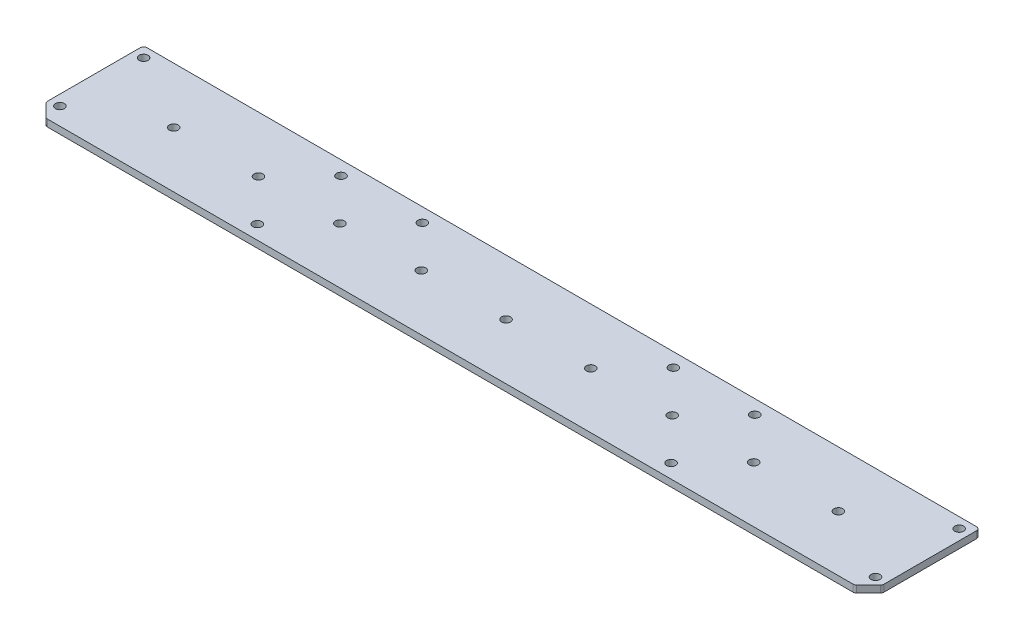
SolidWorks part; units mm, degrees
ref_plane "Front Plane" through (0, 0, 0) normal (0, 0, 1) x (1, 0, 0)
ref_plane "Top Plane" through (0, 0, 0) normal (0, 1, 0) x (1, 0, 0)
ref_plane "Right Plane" through (0, 0, 0) normal (1, 0, 0) x (0, 0, -1)
sketch "Sketch2" plane through (0, 0, 0) normal (0, 1, 0) x (1, 0, 0)
  line L0 (0, 7.0076) -> (0, 50.8)
  line L1 (0, 50.8) -> (381, 50.8)
  line L2 (381, 50.8) -> (381, 7.0076)
  line L3 (373.9924, 0) -> (7.0076, 0)
  line L4 (5.885, 0.465) -> (0.465, 5.885) construction
  line L5 (5.885, 0.465) -> (0.465, 5.885)
  line L6 (375.115, 0.465) -> (380.535, 5.885) construction
  line L7 (375.115, 0.465) -> (380.535, 5.885)
  line L8 (336.537, 50.8) -> (379.4125, 50.8) construction
  arc A0 (5.885, 0.465) -> (7.0076, 0) centre (7.0076, 1.5875) ccw construction
  arc A1 (0, 7.0076) -> (0.465, 5.885) centre (1.5875, 7.0076) ccw construction
  arc A2 (5.885, 0.465) -> (7.0076, 0) centre (7.0076, 1.5875) ccw
  arc A3 (0, 7.0076) -> (0.465, 5.885) centre (1.5875, 7.0076) ccw
  arc A4 (373.9924, 0) -> (375.115, 0.465) centre (373.9924, 1.5875) ccw construction
  arc A6 (373.9924, 0) -> (375.115, 0.465) centre (373.9924, 1.5875) ccw
  arc A8 (380.535, 5.885) -> (381, 7.0076) centre (379.4125, 7.0076) ccw construction
  arc A9 (380.535, 5.885) -> (381, 7.0076) centre (379.4125, 7.0076) ccw
extrude "Boss-Extrude1" add sketch "Sketch2" along normal blind 3.175
sketch "Sketch3" plane through (0, 0, 0) normal (0, 1, 0) x (1, 0, 0)
  circle A25 centre (4.7625, 7.9375) radius 2.032 construction
  circle A31 centre (4.7625, 46.0375) radius 2.032 construction
  circle A63 centre (376.2375, 7.9375) radius 2.032 construction
  circle A64 centre (376.2375, 46.0375) radius 2.032 construction
  circle A67 centre (4.7625, 7.9375) radius 2.032
  circle A68 centre (4.7625, 46.0375) radius 2.032
  circle A72 centre (376.2375, 7.9375) radius 2.032
  circle A73 centre (376.2375, 46.0375) radius 2.032
  circle A123 centre (341.884, 25.4) radius 2.032 construction
  circle A124 centre (247.65, 44.45) radius 2.032 construction
  circle A125 centre (284.734, 44.45) radius 2.032 construction
  circle A129 centre (284.734, 6.35) radius 2.032 construction
  circle A132 centre (190.5, 25.4) radius 2.032 construction
  circle A135 centre (133.35, 44.45) radius 2.032 construction
  circle A136 centre (96.266, 44.45) radius 2.032 construction
  circle A137 centre (96.266, 6.35) radius 2.032 construction
  circle A140 centre (77.724, 25.4) radius 2.032 construction
  circle A141 centre (39.116, 25.4) radius 2.032 construction
  circle A142 centre (341.884, 25.4) radius 2.032
  circle A143 centre (247.65, 44.45) radius 2.032
  circle A144 centre (284.734, 44.45) radius 2.032
  circle A148 centre (284.734, 6.35) radius 2.032
  circle A151 centre (190.5, 25.4) radius 2.032
  circle A154 centre (133.35, 44.45) radius 2.032
  circle A155 centre (96.266, 44.45) radius 2.032
  circle A156 centre (96.266, 6.35) radius 2.032
  circle A159 centre (77.724, 25.4) radius 2.032
  circle A160 centre (39.116, 25.4) radius 2.032
  circle A161 centre (151.892, 25.4) radius 2.032
  circle A162 centre (229.108, 25.4) radius 2.032
  circle A163 centre (266.192, 25.4) radius 2.032
  circle A164 centre (303.276, 25.4) radius 2.032
  circle A165 centre (151.892, 25.4) radius 2.3813 construction
  circle A166 centre (229.108, 25.4) radius 2.3813 construction
  circle A167 centre (266.192, 25.4) radius 2.3813 construction
  circle A168 centre (303.276, 25.4) radius 2.3813 construction
  circle A170 centre (114.808, 25.4) radius 2.032 construction
  circle A171 centre (114.808, 25.4) radius 2.032
extrude "Cut-Extrude1" cut sketch "Sketch3" along normal through all
fillet "Fillet1" radius 1.5875 2 edges at (0, 1.5875, -50.8) (381, 1.5875, -50.8)
